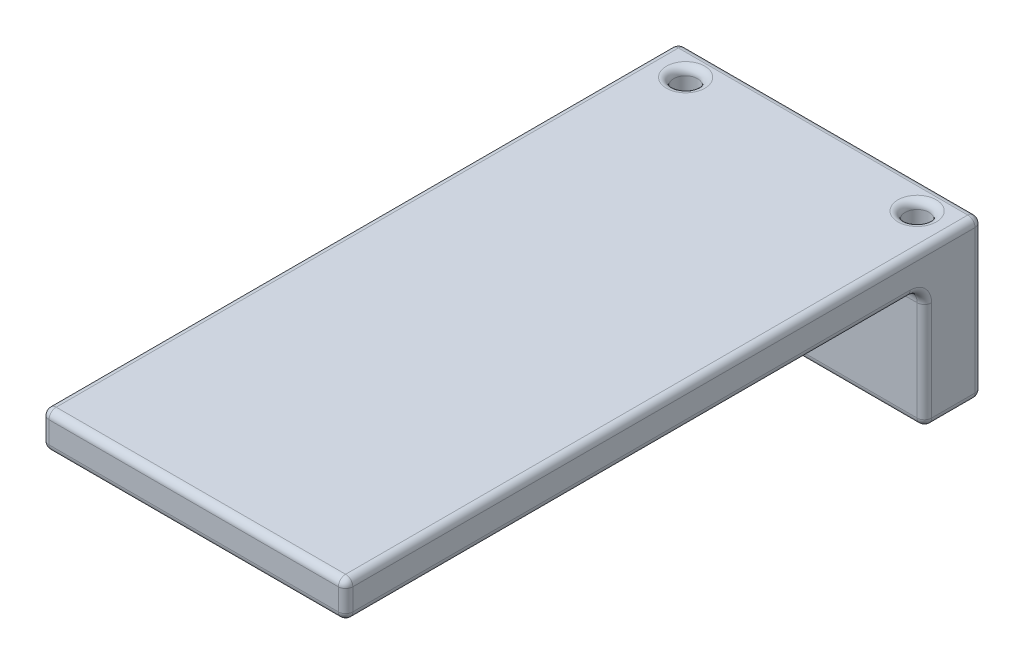
SolidWorks part; units mm, degrees
ref_plane "Front Plane" through (0, 0, 0) normal (0, 0, 1) x (1, 0, 0)
ref_plane "Top Plane" through (0, 0, 0) normal (0, 1, 0) x (1, 0, 0)
ref_plane "Right Plane" through (0, 0, 0) normal (1, 0, 0) x (0, 0, -1)
sketch "Sketch1" plane through (0, 0, 0) normal (0, 1, 0) x (1, 0, 0)
  line L1 (-21, -40) -> (21, -40)
  line L2 (-21, -40) -> (-21, 40)
  line L3 (-21, 40) -> (21, 40)
  line L4 (21, -40) -> (21, 40)
  line L5 (-21, -40) -> (21, 40) construction
  line L6 (-21, 40) -> (21, -40) construction
  point P0 (0, 0)
  dimension "D1" = 42
  dimension "D2" = 80
extrude "Boss-Extrude1" add sketch "Sketch1" along normal blind 5
sketch "Sketch2" plane through (0, 5, 0) normal (0, 1, 0) x (1, 0, 0)
  line L0 (21, -40) -> (21, 40) construction
  line L1 (-21, 40) -> (21, 40)
  line L2 (-21, 40) -> (-21, 48)
  line L3 (-21, 48) -> (21, 48)
  line L4 (21, 40) -> (21, 48)
  circle A0 centre (16, 44) radius 1.4 construction
  circle A1 centre (-16, 44) radius 1.4 construction
  circle A2 centre (16, 44) radius 1.4 construction
  circle A3 centre (-16, 44) radius 1.4 construction
  circle A4 centre (16, 44) radius 1.65
  circle A5 centre (-16, 44) radius 1.65
  dimension "D2" = 3.3
  dimension "D1" = 8
extrude "Boss-Extrude2" add sketch "Sketch2" against normal up to surface (21.8 mm away)
fillet "Fillet1" radius 2 1 edges at (0, 0, -40)
fillet "Fillet2" radius 1 23 edges at (-21, -9.4, -40) (-21, -0.5858, -39.4142) (0, 5, -48) (-21, -5.9, -48) (21, 5, -4) (21, -5.9, -48) (21, -9.4, -40) (21, -0.5858, -39.4142) (16, -16.8, -42.35) (-16, -16.8, -42.35) (0, -16.8, -40) (21, -16.8, -44) (0, -16.8, -48) (-21, -16.8, -44) (21, 0, 1) (-21, 0, 1) (-21, 2.5, 40) (0, 5, 40) (21, 2.5, 40) (0, 0, 40) (-21, 5, -4) (16, 5, -42.35) (-16, 5, -42.35)
